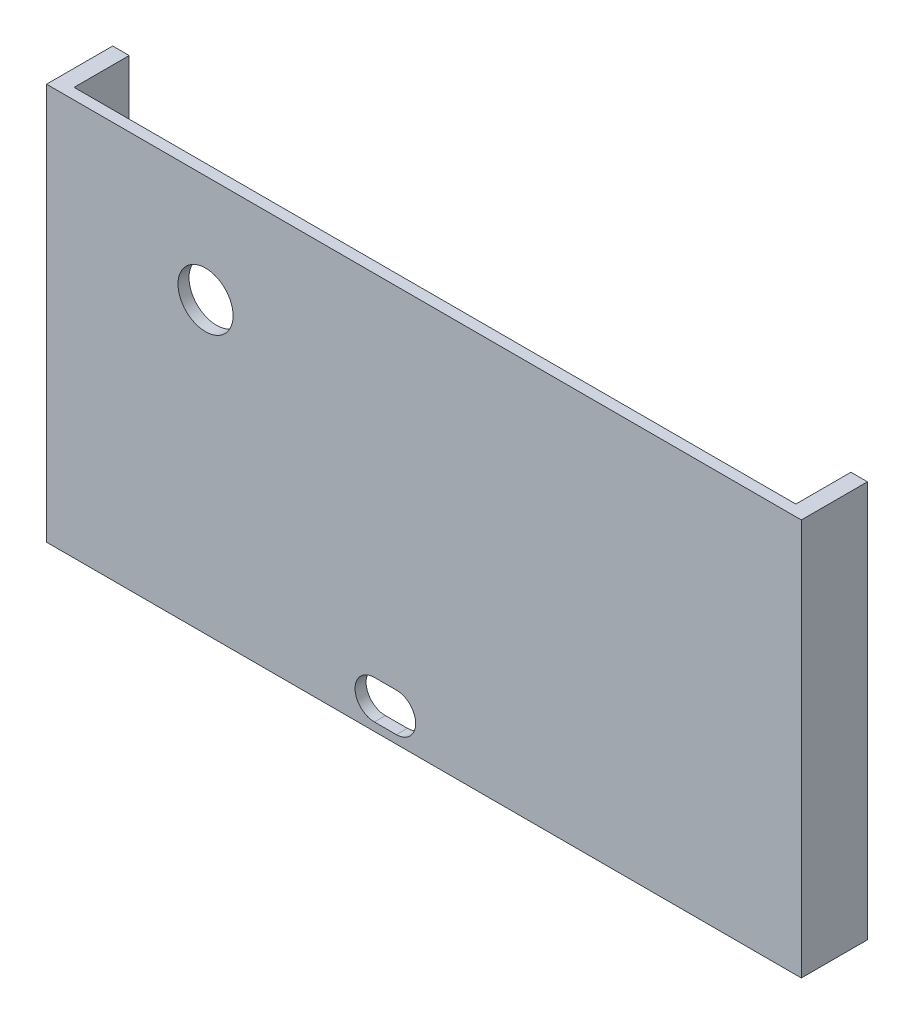
SolidWorks part; units mm, degrees
ref_plane "前视基准面" through (0, 0, 0) normal (0, 0, 1) x (1, 0, 0)
ref_plane "上视基准面" through (0, 0, 0) normal (0, 1, 0) x (1, 0, 0)
ref_plane "右视基准面" through (0, 0, 0) normal (1, 0, 0) x (0, 0, -1)
other "Configuration Table"
sketch "草图1" plane through (0, 0, 0) normal (0, 0, 1) x (1, 0, 0)
  line L1 (-44.837, 41.1121) -> (92.163, 41.1121)
  line L2 (-44.837, 41.1121) -> (-44.837, -30.8879)
  line L3 (-44.837, -30.8879) -> (92.163, -30.8879)
  line L4 (92.163, 41.1121) -> (92.163, -30.8879)
  dimension "D1" = 72
  dimension "D2" = 137
extrude "凸台-拉伸1" add sketch "草图1" along normal blind 2
sketch "草图13" plane through (0, 0, 2) normal (0, 0, 1) x (1, 0, 0)
  circle A0 centre (-15.9792, 21.6315) radius 5
  dimension "D1" = 10
extrude "切除-拉伸3" cut sketch "草图13" against normal blind 10
sketch "草图14" plane through (0, 0, 0) normal (0, 0, -1) x (-1, 0, 0)
  line L0 (15.9792, 21.6315) -> (15.9792, 27.4907) construction
  line L1 (10.9792, 21.6315) -> (10.9792, 26.6315) construction
  line L2 (20.9792, 21.6315) -> (20.9792, 26.6315) construction
  line L3 (15.9792, 25.5402) -> (10.9792, 25.5402) construction
  line L4 (10.9792, 25.5402) -> (20.9792, 25.5402) construction
  line L5 (15.9792, 26.6315) -> (10.9792, 26.6315) construction
  line L6 (15.9792, 26.6315) -> (20.9792, 26.6315) construction
  circle A0 centre (15.9792, 21.6315) radius 5 construction
  circle A1 centre (10.9792, 26.6315) radius 1
  circle A2 centre (20.9792, 26.6315) radius 1
  dimension "D1" = 2
  dimension "D2" = 2
extrude "凸台-拉伸8" add sketch "草图14" along normal blind 5
sketch "草图15" plane through (0, 0, 2) normal (0, 0, 1) x (1, 0, 0)
  line L0 (16.6649, -30.8879) -> (16.6649, -25.8879) construction
  line L2 (14.6649, -25.8879) -> (18.6649, -25.8879) construction
  line L3 (14.6649, -22.3879) -> (18.6649, -22.3879)
  line L4 (14.6649, -29.3879) -> (18.6649, -29.3879)
  arc A0 (14.6649, -22.3879) -> (14.6649, -29.3879) centre (14.6649, -25.8879) ccw
  arc A1 (18.6649, -29.3879) -> (18.6649, -22.3879) centre (18.6649, -25.8879) ccw
  point P6 (16.6649, -25.8879)
  point P11 (11.1649, -25.8879)
  point P12 (22.1649, -25.8879)
  point P13 (0, 0)
  point P15 (-94.6724, 61.0099)
  dimension "D1" = 5
  dimension "D2" = 7
  dimension "D3" = 11
extrude "切除-拉伸4" cut sketch "草图15" against normal blind 5
sketch "草图18" plane through (0, 0, 0) normal (0, 0, -1) x (-1, 0, 0)
  line L0 (-89.163, 38.1121) -> (-89.163, -27.8879)
  line L1 (-92.163, 41.1121) -> (-89.163, 41.1121)
  line L2 (-92.163, 41.1121) -> (-92.163, -30.8879)
  line L3 (-92.163, -30.8879) -> (-89.163, -30.8879)
  line L4 (44.837, 41.1121) -> (44.837, -30.8879)
  line L6 (41.837, 38.1121) -> (41.837, -27.8879)
  line L8 (-89.163, -27.8879) -> (-89.163, -30.8879)
  line L9 (-89.163, 38.1121) -> (-89.163, 41.1121)
  line L10 (41.837, 38.1121) -> (41.837, 41.1121)
  line L11 (41.837, -27.8879) -> (41.837, -30.8879)
  line L12 (41.837, -30.8879) -> (44.837, -30.8879)
  line L13 (-89.163, 38.1121) -> (41.837, 38.1121) construction
  line L14 (-89.163, -27.8879) -> (41.837, -27.8879) construction
  line L15 (41.837, 41.1121) -> (44.837, 41.1121)
  line L16 (-92.163, -30.8879) -> (44.837, -30.8879) construction
  line L18 (-92.163, 41.1121) -> (44.837, 41.1121) construction
  dimension "D1" = 3
extrude "凸台-拉伸9" add sketch "草图18" along normal blind 10
